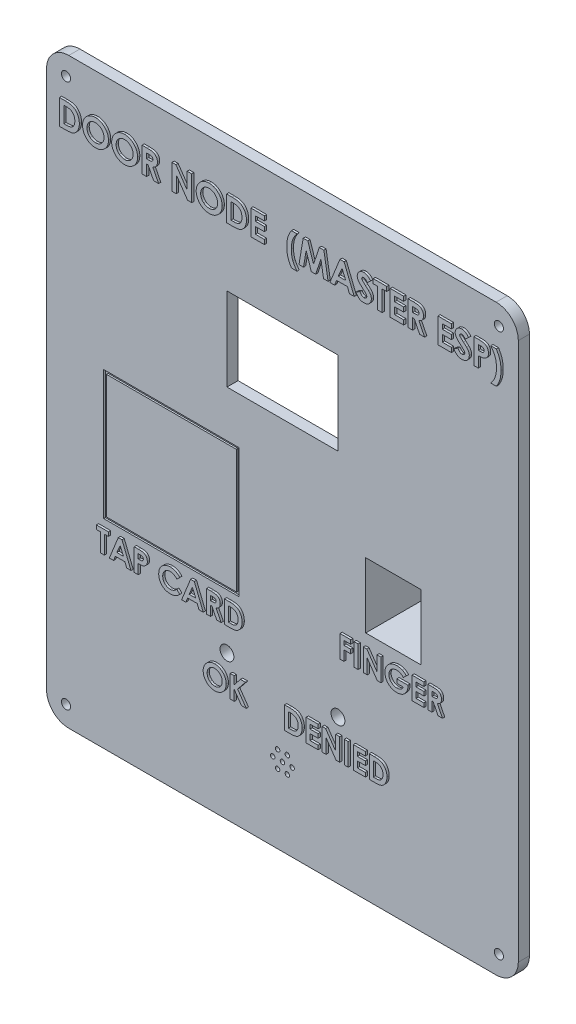
SolidWorks part; units mm, degrees
ref_plane "Front Plane" through (0, 0, 0) normal (0, 0, 1) x (1, 0, 0)
ref_plane "Top Plane" through (0, 0, 0) normal (0, 1, 0) x (1, 0, 0)
ref_plane "Right Plane" through (0, 0, 0) normal (1, 0, 0) x (0, 0, -1)
sketch "Sketch1" plane through (0, 0, 0) normal (0, 0, 1) x (1, 0, 0)
  line L0 (-77, 0) -> (77, 0)
  line L1 (85, 8) -> (85, 202)
  line L2 (77, 210) -> (-77, 210)
  line L3 (-85, 202) -> (-85, 8)
  arc A0 (-85, 8) -> (-77, 0) centre (-77, 8) ccw
  arc A1 (77, 0) -> (85, 8) centre (77, 8) ccw
  arc A2 (85, 202) -> (77, 210) centre (77, 202) ccw
  arc A3 (-77, 210) -> (-85, 202) centre (-77, 202) ccw
extrude "Panel" add sketch "Sketch1" along normal blind 4
ref_plane "P1_Front_4" through (0, 0, 4) normal (0, 0, 1) x (1, 0, 0)
sketch "Sketch2" plane through (0, 0, 0) normal (0, 0, 1) x (1, 0, 0)
  circle A0 centre (-78, 7) radius 1.65
  circle A1 centre (78, 7) radius 1.65
  circle A2 centre (-78, 203) radius 1.65
  circle A3 centre (78, 203) radius 1.65
extrude "Screw holes" cut sketch "Sketch2" along normal through all
ref_plane "P2_Front_-3" through (0, 0, -3) normal (0, 0, 1) x (1, 0, 0)
sketch "Sketch3" plane through (0, 0, -3) normal (0, 0, 1) x (1, 0, 0)
  line L1 (-15, 3.3) -> (15, 3.3)
  line L2 (-15, 3.3) -> (-15, 5.3)
  line L3 (-15, 5.3) -> (15, 5.3)
  line L4 (15, 3.3) -> (15, 5.3)
  line L6 (-15, 204.7) -> (15, 204.7)
  line L7 (-15, 204.7) -> (-15, 206.7)
  line L8 (-15, 206.7) -> (15, 206.7)
  line L9 (15, 204.7) -> (15, 206.7)
  line L11 (-81.7, 90) -> (-79.7, 90)
  line L12 (-81.7, 90) -> (-81.7, 120)
  line L13 (-81.7, 120) -> (-79.7, 120)
  line L14 (-79.7, 90) -> (-79.7, 120)
  line L16 (79.7, 90) -> (81.7, 90)
  line L17 (79.7, 90) -> (79.7, 120)
  line L18 (79.7, 120) -> (81.7, 120)
  line L19 (81.7, 90) -> (81.7, 120)
extrude "Locating tabs" add sketch "Sketch3" along normal blind 3
sketch "Sketch4" plane through (0, 0, 0) normal (0, 0, 1) x (1, 0, 0)
  line L1 (-20, 135) -> (20, 135)
  line L2 (-20, 135) -> (-20, 165)
  line L3 (-20, 165) -> (20, 165)
  line L4 (20, 135) -> (20, 165)
  line L5 (-20, 135) -> (20, 165) construction
  line L6 (-20, 165) -> (20, 135) construction
  point P0 (0, 150)
extrude "TFT window" cut sketch "Sketch4" along normal through all
ref_plane "P3_Front_-2.4" through (0, 0, -2.4) normal (0, 0, 1) x (1, 0, 0)
sketch "Sketch5" plane through (0, 0, -2.4) normal (0, 0, 1) x (1, 0, 0)
  circle A0 centre (-26, 135.75) radius 2.1
  circle A1 centre (-26, 164.25) radius 2.1
  circle A2 centre (26, 135.75) radius 2.1
  circle A3 centre (26, 164.25) radius 2.1
extrude "TFT bosses" add sketch "Sketch5" along normal blind 2.4
ref_plane "P4_Front_-2.4" through (0, 0, -2.4) normal (0, 0, 1) x (1, 0, 0)
sketch "Sketch6" plane through (0, 0, -2.4) normal (0, 0, 1) x (1, 0, 0)
  circle A0 centre (-26, 135.75) radius 1.1
  circle A1 centre (-26, 164.25) radius 1.1
  circle A2 centre (26, 135.75) radius 1.1
  circle A3 centre (26, 164.25) radius 1.1
extrude "TFT pilot holes" cut sketch "Sketch6" along normal blind 4
sketch "Sketch7" plane through (0, 0, 0) normal (0, 0, 1) x (1, 0, 0)
  line L1 (-61.425, 74.74) -> (-18.575, 74.74)
  line L2 (-61.425, 74.74) -> (-61.425, 115.26)
  line L3 (-61.425, 115.26) -> (-18.575, 115.26)
  line L4 (-18.575, 74.74) -> (-18.575, 115.26)
  line L5 (-61.425, 74.74) -> (-18.575, 115.26) construction
  line L6 (-61.425, 115.26) -> (-18.575, 74.74) construction
  circle A0 centre (-53.9, 82.4) radius 3
  circle A1 centre (-53.9, 107.6) radius 3
  circle A2 centre (-26.1, 82.4) radius 3
  circle A3 centre (-26.1, 107.6) radius 3
  point P0 (-40, 95)
extrude "NFC pocket" cut sketch "Sketch7" along normal blind 2.5
sketch "Sketch8" plane through (0, 0, 0) normal (0, 0, 1) x (1, 0, 0)
  circle A0 centre (-53.9, 82.4) radius 1.1
  circle A1 centre (-53.9, 107.6) radius 1.1
  circle A2 centre (-26.1, 82.4) radius 1.1
  circle A3 centre (-26.1, 107.6) radius 1.1
extrude "NFC pilot holes" cut sketch "Sketch8" along normal blind 3
sketch "Sketch9" plane through (0, 0, 4) normal (0, 0, 1) x (1, 0, 0)
  line L1 (-64.425, 71.74) -> (-15.575, 71.74)
  line L2 (-64.425, 71.74) -> (-64.425, 118.26)
  line L3 (-64.425, 118.26) -> (-15.575, 118.26)
  line L4 (-15.575, 71.74) -> (-15.575, 118.26)
  line L5 (-64.425, 71.74) -> (-15.575, 118.26) construction
  line L6 (-64.425, 118.26) -> (-15.575, 71.74) construction
  point P0 (-40, 95)
extrude "NFC tap outline recess" cut sketch "Sketch9" against normal blind 0.6
ref_plane "P5_Front_3.4" through (0, 0, 3.4) normal (0, 0, 1) x (1, 0, 0)
sketch "Sketch10" plane through (0, 0, 3.4) normal (0, 0, 1) x (1, 0, 0)
  line L1 (-63.425, 72.74) -> (-16.575, 72.74)
  line L2 (-63.425, 72.74) -> (-63.425, 117.26)
  line L3 (-63.425, 117.26) -> (-16.575, 117.26)
  line L4 (-16.575, 72.74) -> (-16.575, 117.26)
  line L5 (-63.425, 72.74) -> (-16.575, 117.26) construction
  line L6 (-63.425, 117.26) -> (-16.575, 72.74) construction
  point P0 (-40, 95)
extrude "NFC tap outline fill" add sketch "Sketch10" along normal blind 0.6
sketch "Sketch11" plane through (0, 0, 0) normal (0, 0, 1) x (1, 0, 0)
  line L1 (30, 83.25) -> (50, 83.25)
  line L2 (30, 83.25) -> (30, 106.75)
  line L3 (30, 106.75) -> (50, 106.75)
  line L4 (50, 83.25) -> (50, 106.75)
  line L5 (30, 83.25) -> (50, 106.75) construction
  line L6 (30, 106.75) -> (50, 83.25) construction
  point P0 (40, 95)
extrude "Fingerprint opening" cut sketch "Sketch11" along normal through all
ref_plane "P6_Front_-25.1" through (0, 0, -25.1) normal (0, 0, 1) x (1, 0, 0)
sketch "Sketch12" plane through (0, 0, -25.1) normal (0, 0, 1) x (1, 0, 0)
  line L1 (27.5, 80.75) -> (52.5, 80.75)
  line L2 (27.5, 80.75) -> (27.5, 109.25)
  line L3 (27.5, 109.25) -> (52.5, 109.25)
  line L4 (52.5, 80.75) -> (52.5, 109.25)
  line L5 (27.5, 80.75) -> (52.5, 109.25) construction
  line L6 (27.5, 109.25) -> (52.5, 80.75) construction
  line L7 (30, 83.25) -> (50, 83.25)
  line L8 (30, 83.25) -> (30, 106.75)
  line L9 (30, 106.75) -> (50, 106.75)
  line L10 (50, 83.25) -> (50, 106.75)
  line L11 (30, 83.25) -> (50, 106.75) construction
  line L12 (30, 106.75) -> (50, 83.25) construction
  point P0 (40, 95)
  point P5 (40, 95)
extrude "Fingerprint sleeve" add sketch "Sketch12" along normal blind 25.1
ref_plane "P7_Front_-27.1" through (0, 0, -27.1) normal (0, 0, 1) x (1, 0, 0)
sketch "Sketch13" plane through (0, 0, -27.1) normal (0, 0, 1) x (1, 0, 0)
  line L1 (27.5, 80.75) -> (33, 80.75)
  line L2 (27.5, 80.75) -> (27.5, 109.25)
  line L3 (27.5, 109.25) -> (33, 109.25)
  line L4 (33, 80.75) -> (33, 109.25)
  line L6 (47, 80.75) -> (52.5, 80.75)
  line L7 (47, 80.75) -> (47, 109.25)
  line L8 (47, 109.25) -> (52.5, 109.25)
  line L9 (52.5, 80.75) -> (52.5, 109.25)
extrude "Fingerprint back stop" add sketch "Sketch13" along normal blind 2
ref_plane "P8_Top_110.25" through (0, 110.25, 0) normal (0, 1, 0) x (1, 0, 0)
sketch "Sketch14" plane through (0, 110.25, 0) normal (0, 1, 0) x (1, 0, 0)
  circle A0 centre (40, 12.55) radius 1.1
extrude "Fingerprint clamp screw pilot" cut sketch "Sketch14" against normal through all
sketch "Sketch15" plane through (0, 0, 0) normal (0, 0, 1) x (1, 0, 0)
  circle A0 centre (-20, 52) radius 2.5
  circle A1 centre (20, 52) radius 2.5
extrude "LED holes" cut sketch "Sketch15" along normal through all
sketch "Sketch16" plane through (0, 0, 0) normal (0, 0, 1) x (1, 0, 0)
  circle A0 centre (0, 28) radius 0.8
  circle A1 centre (3.5, 28) radius 0.8
  circle A2 centre (1.75, 31.0311) radius 0.8
  circle A3 centre (-1.75, 31.0311) radius 0.8
  circle A4 centre (-3.5, 28) radius 0.8
  circle A5 centre (-1.75, 24.9689) radius 0.8
  circle A6 centre (1.75, 24.9689) radius 0.8
extrude "Buzzer sound holes" cut sketch "Sketch16" along normal through all
ref_plane "P9_Front_-7" through (0, 0, -7) normal (0, 0, 1) x (1, 0, 0)
sketch "Sketch17" plane through (0, 0, -7) normal (0, 0, 1) x (1, 0, 0)
  circle A0 centre (0, 28) radius 7.7
  circle A1 centre (0, 28) radius 6.1
extrude "Buzzer cradle" add sketch "Sketch17" along normal blind 7
sketch "Sketch18" plane through (0, 0, 4) normal (0, 0, 1) x (1, 0, 0)
  text T0 "DOOR NODE  (MASTER ESP)" font "Century Gothic" height 9
  text T1 "TAP CARD" font "Century Gothic" height 8
  text T2 "FINGER" font "Century Gothic" height 8
  text T3 "OK" font "Century Gothic" height 8
  text T4 "DENIED" font "Century Gothic" height 8
extrude "Labels (raised)" add sketch "Sketch18" along normal blind 0.8
